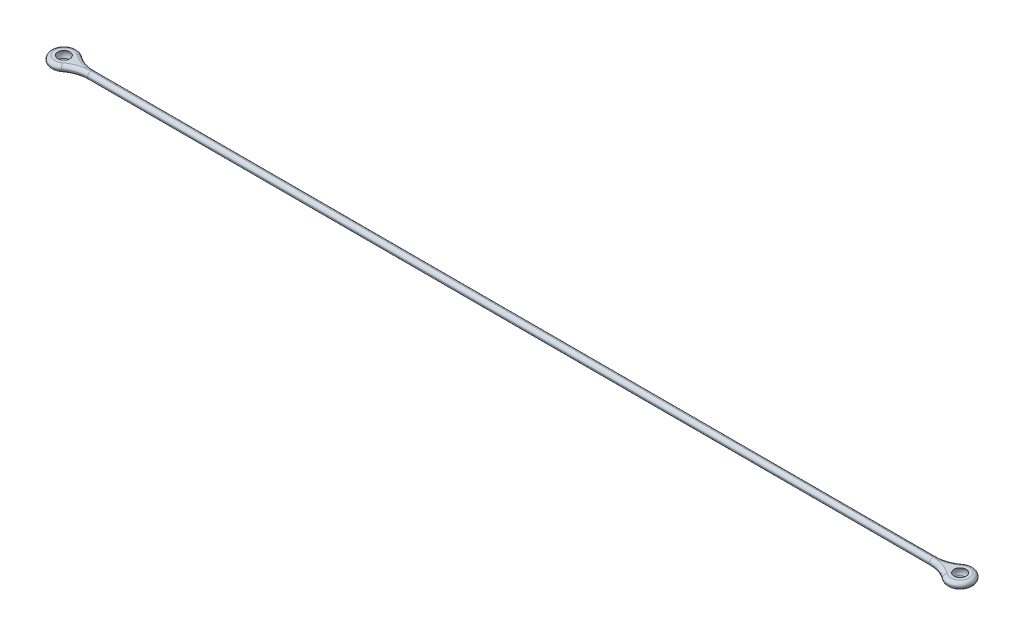
SolidWorks part; units mm, degrees
ref_plane "Front Plane" through (0, 0, 0) normal (0, 0, 1) x (1, 0, 0)
ref_plane "Top Plane" through (0, 0, 0) normal (0, 1, 0) x (1, 0, 0)
ref_plane "Right Plane" through (0, 0, 0) normal (1, 0, 0) x (0, 0, -1)
sketch "Sketch1" plane through (0, 0, 0) normal (0, 1, 0) x (1, 0, 0)
  line L0 (-97.157, 0) -> (97.157, 0) construction
  line L1 (-97.157, 0) -> (97.157, 0) construction
  line L2 (-97.157, 2.75) -> (97.157, 2.75)
  line L3 (-97.157, -2.75) -> (97.157, -2.75) construction
  line L4 (91.2671, -2.75) -> (91.2671, 2.75) construction
  line L5 (-91.2671, -0.75) -> (91.2671, -0.75)
  line L6 (-91.2671, -0.75) -> (-91.2671, 0.75) construction
  line L7 (-91.2671, 0.75) -> (91.2671, 0.75)
  line L8 (91.2671, -0.75) -> (91.2671, 0.75)
  line L9 (-91.2671, -0.75) -> (91.2671, 0.75) construction
  line L10 (-91.2671, 0.75) -> (91.2671, -0.75) construction
  line L11 (-91.2671, -2.75) -> (-91.2671, 2.75) construction
  line L12 (-98.657, 0) -> (-95.657, 0)
  line L13 (95.657, 0) -> (98.657, 0)
  circle A0 centre (-97.157, 0) radius 1.5
  circle A1 centre (97.157, 0) radius 1.5
  arc A2 (-97.157, 2.75) -> (-97.157, -2.75) centre (-97.157, 0) ccw
  arc A3 (97.157, -2.75) -> (97.157, 2.75) centre (97.157, 0) ccw
  arc A4 (91.2671, -0.75) -> (95.4825, -2.1814) centre (91.2671, -7.6728) cw
  arc A5 (97.157, -2.75) -> (95.4825, -2.1814) centre (97.157, 0) cw
  arc A6 (97.157, 2.75) -> (95.4825, 2.1814) centre (97.157, 0) ccw
  arc A7 (91.2671, 0.75) -> (95.4825, 2.1814) centre (91.2671, 7.6728) ccw
  arc A8 (-97.157, -2.75) -> (-95.4825, -2.1814) centre (-97.157, 0) ccw
  arc A9 (-97.157, 2.75) -> (-95.4825, 2.1814) centre (-97.157, 0) cw
  arc A10 (-91.2671, 0.75) -> (-95.4825, 2.1814) centre (-91.2671, 7.6728) cw
  arc A11 (-91.2671, -0.75) -> (-95.4825, -2.1814) centre (-91.2671, -7.6728) ccw
  point P4 (0, 0)
  point P10 (0, 0)
  dimension "D1" = 3
  dimension "D4" = 2.75
  dimension "D2" = 194.314
  dimension "D5" = 1.5
extrude "Boss-Extrude1" add sketch "Sketch1" along normal blind 0.75 and the other way blind 0.75 contours L2 A2 L3 L11 L6 A0 | L3 A3 L2 L4 A1 | A0 | A1 | L7 L6 L5 L4 | L12 A0 | L13 A1 region at (-7.611, 0, 0) region at (99.8046, 0, 0) region at (-97.157, 0, -0.6366) region at (-97.157, 0, 0.6366) region at (97.157, 0, -0.6366) region at (97.157, 0, 0.6366)
revolve "Cut-Revolve1" cut sketch "Sketch1<3>" angle 360 about L0 region at (-97.157, 0, 0.6366) region at (97.157, 0, 0.6366)
sketch "Sketch1<3>" plane through (0, 0, 0) normal (0, 1, 0) x (1, 0, 0) same geometry as "Sketch1"
fillet "Fillet1" radius 0.75 16 edges at (-93.493, -0.75, 1.1176) (-99.907, -0.75, 0) (-93.493, -0.75, -1.1176) (0, -0.75, -0.75) (93.493, -0.75, -1.1176) (99.907, -0.75, 0) (93.493, -0.75, 1.1176) (-93.493, 0.75, 1.1176) (-99.907, 0.75, 0) (-93.493, 0.75, -1.1176) (0, 0.75, -0.75) (93.493, 0.75, -1.1176) (99.907, 0.75, 0) (93.493, 0.75, 1.1176) (0, -0.75, 0.75) (0, 0.75, 0.75)
